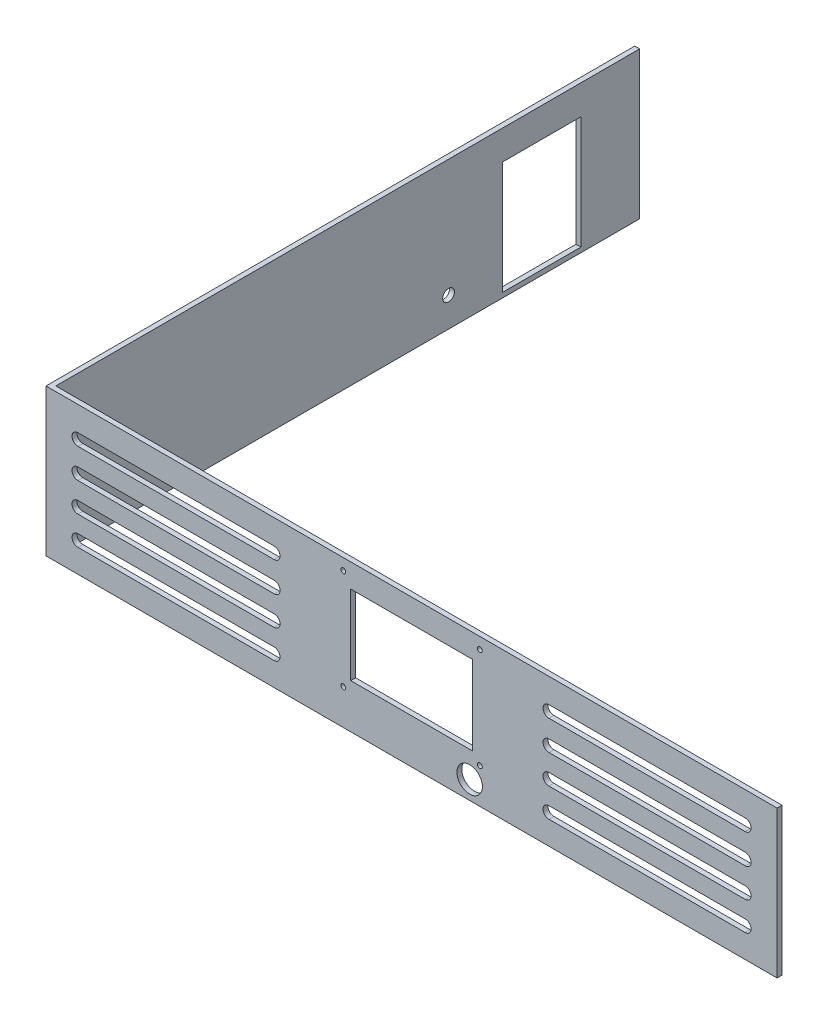
SolidWorks part; units mm, degrees
ref_plane "Front Plane" through (0, 0, 0) normal (0, 0, 1) x (1, 0, 0)
ref_plane "Top Plane" through (0, 0, 0) normal (0, 1, 0) x (1, 0, 0)
ref_plane "Right Plane" through (0, 0, 0) normal (1, 0, 0) x (0, 0, -1)
sketch "Sketch1" plane through (0, 0, 0) normal (0, 0, 1) x (1, 0, 0)
  line L1 (-236.5375, -47.625) -> (236.5375, -47.625)
  line L2 (-236.5375, -47.625) -> (-236.5375, 47.625)
  line L3 (-236.5375, 47.625) -> (236.5375, 47.625)
  line L4 (236.5375, -47.625) -> (236.5375, 47.625)
  line L5 (-236.5375, -47.625) -> (236.5375, 47.625) construction
  line L6 (-236.5375, 47.625) -> (236.5375, -47.625) construction
  point P0 (0, 0)
  dimension "D1" = 473.075
  dimension "D2" = 95.25
extrude "Boss-Extrude1" add sketch "Sketch1" along normal blind 3.175
sketch "Sketch3" plane through (0, 0, 3.175) normal (0, 0, 1) x (1, 0, 0)
  line L0 (0, -47.625) -> (0, -19.05)
  line L1 (-236.5375, -47.625) -> (236.5375, -47.625) construction
  line L3 (-39.37, -18.923) -> (39.37, -18.923)
  line L4 (-39.37, -18.923) -> (-39.37, 32.385)
  line L5 (-39.37, 32.385) -> (39.37, 32.385)
  line L6 (39.37, -18.923) -> (39.37, 32.385)
  dimension "D1" = 28.575
  dimension "D2" = 78.74
  dimension "D3" = 39.37
  dimension "D4" = 51.308
  dimension "D5" = 28.702
extrude "Cut-Extrude2" cut sketch "Sketch3" against normal through all contours L3 L6 L5 L4 region at (0, 6.731, 3.175)
sketch "Sketch4" plane through (0, 0, 3.175) normal (0, 0, 1) x (1, 0, 0)
  line L0 (-236.5375, -47.625) -> (236.5375, -47.625) construction
  line L1 (39.37, -18.923) -> (39.37, 32.385) construction
  circle A0 centre (37.592, -35.814) radius 8.255
  dimension "D1" = 16.51
  dimension "D2" = 11.811
  dimension "D3" = 1.778
extrude "Cut-Extrude3" cut sketch "Sketch4" against normal through all
sketch "Sketch5" plane through (0, 0, 3.175) normal (0, 0, 1) x (1, 0, 0)
  line L0 (39.37, -18.923) -> (39.37, 32.385) construction
  line L1 (-39.37, 32.385) -> (39.37, 32.385) construction
  line L2 (0, 0) -> (0, 11.1381)
  line L3 (0, 0) -> (6.9433, 0)
  circle A0 centre (44.196, 40.259) radius 1.5875
  circle A1 centre (44.196, -24.765) radius 1.5875
  circle A2 centre (-44.196, -24.765) radius 1.5875
  circle A3 centre (-44.196, 40.259) radius 1.5875
  dimension "D1" = 3.175
  dimension "D3" = 7.874
  dimension "D4" = 65.024
  dimension "D5" = 0
  dimension "D2" = 4.826
extrude "Cut-Extrude4" cut sketch "Sketch5" against normal through all contours A3 | A0 | A2 | A1 region at (44.196, 40.259, 3.175) region at (44.196, -24.765, 3.175) region at (-44.196, -24.765, 3.175) region at (-44.196, 40.259, 3.175)
sketch "Sketch6" plane through (0, 0, 0) normal (0, 0, -1) x (-1, 0, 0)
  line L0 (236.5375, -47.625) -> (-236.5375, -47.625) construction
  line L1 (236.5375, 47.625) -> (233.3625, 47.625)
  line L2 (236.5375, 47.625) -> (236.5375, -47.625)
  line L3 (236.5375, -47.625) -> (233.3625, -47.625)
  line L4 (233.3625, 47.625) -> (233.3625, -47.625)
  dimension "D1" = 3.175
extrude "Boss-Extrude2" add sketch "Sketch6" along normal blind 377.825
sketch "Sketch7" plane through (-236.5375, 0, 0) normal (-1, 0, 0) x (0, 0, 1)
  line L0 (3.175, 47.625) -> (-377.825, 47.625) construction
  line L1 (-339.725, 28.575) -> (-288.925, 28.575)
  line L2 (-339.725, 28.575) -> (-339.725, -44.45)
  line L3 (-339.725, -44.45) -> (-288.925, -44.45)
  line L4 (-288.925, 28.575) -> (-288.925, -44.45)
  line L5 (-377.825, -47.625) -> (-377.825, 47.625) construction
  line L6 (3.175, -47.625) -> (-377.825, -47.625) construction
  circle A0 centre (-254.127, -28.575) radius 3.81
  dimension "D5" = 123.698
  dimension "D6" = 19.05
  dimension "D1" = 19.05
  dimension "D2" = 50.8
  dimension "D3" = 38.1
  dimension "D4" = 3.175
extrude "Cut-Extrude5" cut sketch "Sketch7" against normal blind 381
sketch "Sketch8" plane through (0, 0, 3.175) normal (0, 0, 1) x (1, 0, 0)
  line L0 (88.9, 27.94) -> (215.9, 27.94) construction
  line L1 (88.9, 31.75) -> (215.9, 31.75)
  line L2 (88.9, 24.13) -> (215.9, 24.13)
  line L3 (88.9, 8.7536) -> (215.9, 8.7536) construction
  line L4 (88.9, 12.5636) -> (215.9, 12.5636)
  line L5 (88.9, 4.9436) -> (215.9, 4.9436)
  line L6 (88.9, -10.0663) -> (215.9, -10.0663) construction
  line L7 (88.9, -6.2563) -> (215.9, -6.2563)
  line L8 (88.9, -13.8763) -> (215.9, -13.8763)
  line L9 (88.9, -28.656) -> (215.9, -28.656) construction
  line L10 (88.9, -24.846) -> (215.9, -24.846)
  line L11 (88.9, -32.466) -> (215.9, -32.466)
  line L15 (-88.9, -28.656) -> (-215.9, -28.656) construction
  line L18 (-88.9, -24.846) -> (-215.9, -24.846)
  line L21 (-88.9, -32.466) -> (-215.9, -32.466)
  line L24 (-88.9, -10.0663) -> (-215.9, -10.0663) construction
  line L27 (-88.9, -6.2563) -> (-215.9, -6.2563)
  line L28 (-88.9, -13.8763) -> (-215.9, -13.8763)
  line L29 (-88.9, 8.7536) -> (-215.9, 8.7536) construction
  line L30 (-88.9, 12.5636) -> (-215.9, 12.5636)
  line L31 (-88.9, 4.9436) -> (-215.9, 4.9436)
  line L32 (-88.9, 27.94) -> (-215.9, 27.94) construction
  line L33 (-88.9, 31.75) -> (-215.9, 31.75)
  line L34 (-88.9, 24.13) -> (-215.9, 24.13)
  arc A0 (88.9, 31.75) -> (88.9, 24.13) centre (88.9, 27.94) ccw
  arc A1 (215.9, 24.13) -> (215.9, 31.75) centre (215.9, 27.94) ccw
  arc A2 (88.9, 12.5636) -> (88.9, 4.9436) centre (88.9, 8.7536) ccw
  arc A3 (215.9, 4.9436) -> (215.9, 12.5636) centre (215.9, 8.7536) ccw
  arc A4 (88.9, -6.2563) -> (88.9, -13.8763) centre (88.9, -10.0663) ccw
  arc A5 (215.9, -13.8763) -> (215.9, -6.2563) centre (215.9, -10.0663) ccw
  arc A6 (88.9, -24.846) -> (88.9, -32.466) centre (88.9, -28.656) ccw
  arc A7 (215.9, -32.466) -> (215.9, -24.846) centre (215.9, -28.656) ccw
  arc A16 (-88.9, -24.846) -> (-88.9, -32.466) centre (-88.9, -28.656) cw
  arc A17 (-215.9, -32.466) -> (-215.9, -24.846) centre (-215.9, -28.656) cw
  arc A18 (-88.9, -6.2563) -> (-88.9, -13.8763) centre (-88.9, -10.0663) cw
  arc A19 (-215.9, -13.8763) -> (-215.9, -6.2563) centre (-215.9, -10.0663) cw
  arc A20 (-88.9, 12.5636) -> (-88.9, 4.9436) centre (-88.9, 8.7536) cw
  arc A21 (-215.9, 4.9436) -> (-215.9, 12.5636) centre (-215.9, 8.7536) cw
  arc A22 (-88.9, 31.75) -> (-88.9, 24.13) centre (-88.9, 27.94) cw
  arc A23 (-215.9, 24.13) -> (-215.9, 31.75) centre (-215.9, 27.94) cw
  point P2 (152.4, 27.94)
  point P7 (152.4, 8.7536)
  point P16 (152.4, -10.0663)
  point P21 (152.4, -28.656)
  point P32 (-152.4, -28.656)
  point P39 (-152.4, -10.0663)
  point P46 (-152.4, 8.7536)
  point P53 (-152.4, 27.94)
extrude "Cut-Extrude6" cut sketch "Sketch8" against normal blind 381 contours L11 A7 L10 A6 | L8 A5 L7 A4 | L5 A3 L4 A2 | L2 A1 L1 A0 | L2 A1 L1 A0 | L33 A23 L34 A22 | L30 A21 L31 A20 | L27 A19 L28 A18 | L18 A17 L21 A16 region at (152.4, 27.94, 3.175) region at (152.4, 8.7536, 3.175) region at (152.4, -10.0663, 3.175) region at (152.4, -28.656, 3.175)
